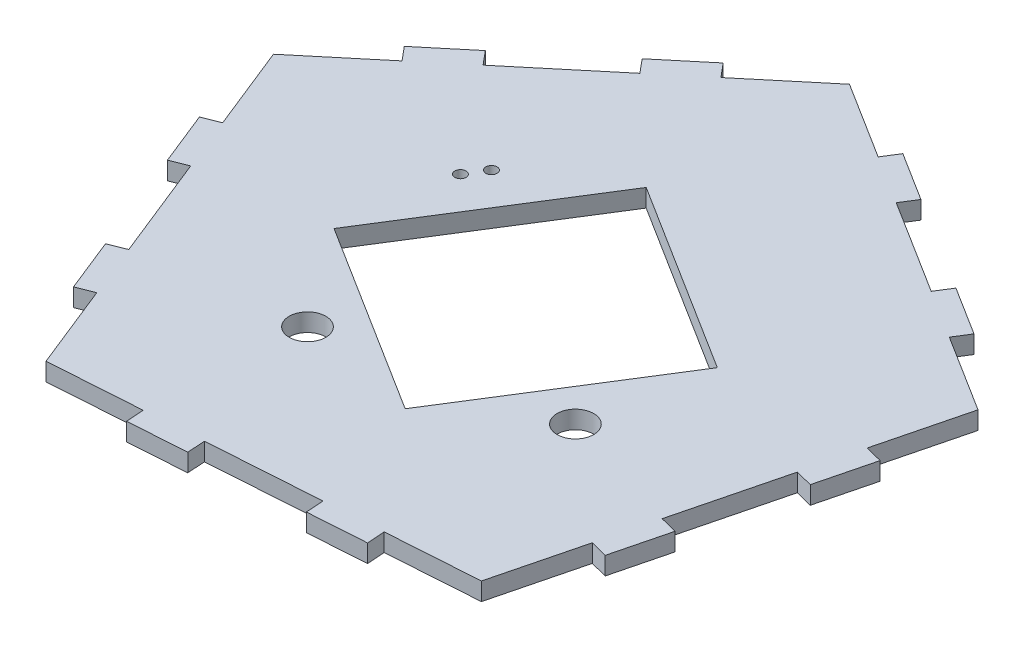
SolidWorks part; units mm, degrees
ref_plane "Front Plane" through (0, 0, 0) normal (0, 0, 1) x (1, 0, 0)
ref_plane "Top Plane" through (0, 0, 0) normal (0, 1, 0) x (1, 0, 0)
ref_plane "Right Plane" through (0, 0, 0) normal (1, 0, 0) x (0, 0, -1)
sketch "Sketch1" plane through (0, 0, 0) normal (0, 1, 0) x (1, 0, 0)
  line L1 (-59.9258, 15.1181) -> (-32.8962, -52.3211)
  line L2 (-32.8962, -52.3211) -> (39.5948, -47.4543)
  line L3 (39.5948, -47.4543) -> (57.3672, 22.9927)
  line L4 (57.3672, 22.9927) -> (-4.14, 61.6646)
  line L5 (-4.14, 61.6646) -> (-59.9258, 15.1181)
  circle A0 centre (0, 0) radius 50 construction
  dimension "D1" = 100
extrude "Boss-Extrude1" add sketch "Sketch1" along normal blind 3.18
ref_axis "Axis" through (0, 3.339, 0) along (0, -1, 0)
sketch "Axis Check" plane through (0, 3.18, 0) normal (0, 1, 0) x (1, 0, 0)
  line L0 (3.3493, -49.8877) -> (-4.14, 61.6646) construction
  line L1 (-32.8962, -52.3211) -> (39.5948, -47.4543) construction
  line L2 (57.3672, 22.9927) -> (-46.411, -18.6015) construction
  line L3 (-59.9258, 15.1181) -> (-32.8962, -52.3211) construction
  line L4 (-32.0329, 38.3913) -> (39.5948, -47.4543) construction
  line L5 (-4.14, 61.6646) -> (-59.9258, 15.1181) construction
  line L6 (-59.9258, 15.1181) -> (48.481, -12.2308) construction
  line L7 (39.5948, -47.4543) -> (57.3672, 22.9927) construction
  line L8 (-32.8962, -52.3211) -> (26.6136, 42.3287) construction
  line L9 (57.3672, 22.9927) -> (-4.14, 61.6646) construction
sketch "Sketch2" plane through (0, 0, 0) normal (0, -1, 0) x (1, 0, 0)
  line L0 (-53.8107, 0.1392) -> (-50.859, -1.0438)
  line L1 (-53.8107, 0.1392) -> (-50.1723, 9.2172)
  line L2 (-50.859, -1.0438) -> (-47.2205, 8.0342)
  line L3 (-50.1723, 9.2172) -> (-47.2205, 8.0342)
  line L4 (-59.9258, -15.1181) -> (-32.8962, 52.3211) construction
  line L5 (-42.6498, 27.9858) -> (-39.0113, 37.0638)
  line L6 (-42.6498, 27.9858) -> (-39.6981, 26.8028)
  line L7 (-39.0113, 37.0638) -> (-36.0596, 35.8808)
  line L8 (-39.6981, 26.8028) -> (-36.0596, 35.8808)
  line L9 (-46.411, 18.6015) -> (-19.2439, 7.7129) construction
  line L10 (-40.8306, 32.5248) -> (-37.8788, 31.3418) construction
  dimension "D1" = 3.18
  dimension "D2" = 9.78
  dimension "D3" = 10.11
extrude "Cut F" [suppressed] cut sketch "Sketch2" against normal through all
sketch "Sketch4" plane through (0, 3.18, 0) normal (0, 1, 0) x (1, 0, 0)
  line L9 (26.6136, 42.3287) -> (-26.6136, -42.3287) construction
  line L10 (57.3672, 22.9927) -> (-4.14, 61.6646) construction
  line L11 (-27.7286, -6.3206) -> (-6.3206, 27.7286)
  line L12 (-27.7286, -6.3206) -> (6.3206, -27.7286)
  line L13 (-6.3206, 27.7286) -> (27.7286, 6.3206)
  line L14 (6.3206, -27.7286) -> (27.7286, 6.3206)
  line L15 (-27.7286, -6.3206) -> (27.7286, 6.3206) construction
  line L16 (-6.3206, 27.7286) -> (6.3206, -27.7286) construction
  line L20 (0, 0) -> (39.0006, -24.5211) construction
  circle A0 centre (-14.9622, -23.7972) radius 3.25
  circle A1 centre (23.7972, -14.9622) radius 3.25
  point P5 (0, 0)
  point P6 (-14.9622, -23.7972)
  dimension "D3" = 6.5
  dimension "D1" = 40.22
  dimension "D2" = 40.22
  dimension "D4" = 8
  dimension "D5" = 8
extrude "Top Cut" cut sketch "Sketch4" against normal blind 10
sketch "Sketch7" plane through (0, 3.18, 0) normal (0, 1, 0) x (1, 0, 0)
  line L0 (0, 0) -> (26.6136, 42.3287) construction
  line L1 (57.3672, 22.9927) -> (-4.14, 61.6646) construction
  line L2 (1.0645, 1.6931) -> (-22.7326, 16.6553) construction
  line L3 (-6.1086, 1.4782) -> (-24.8617, 13.269) construction
  line L5 (-6.3206, 27.7286) -> (-27.7286, -6.3206) construction
  circle A0 centre (-22.7326, 16.6553) radius 1
  circle A1 centre (-24.8617, 13.269) radius 1
  dimension "D5" = 2
  dimension "D1" = 4
  dimension "D2" = 2
  dimension "D3" = 8
  dimension "D4" = 8
extrude "Top Cut 2" cut sketch "Sketch7" against normal through all
sketch "Bottom Cut" [suppressed] plane through (0, 3.18, 0) normal (0, 1, 0) x (1, 0, 0)
  line L0 (3.3493, -49.8877) -> (-4.14, 61.6646) construction
  line L2 (-32.8962, -52.3211) -> (39.5948, -47.4543) construction
  line L5 (-33.7535, -23.9959) -> (-33.7535, 24.3041) construction
  circle A4 centre (-33.7535, -23.9959) radius 1.6
  circle A5 centre (-32.1535, 24.3041) radius 1.6
  circle A6 centre (18.6465, 9.0041) radius 1.6
  circle A7 centre (18.6465, -18.8959) radius 1.6
  dimension "D1" = 3.2
  dimension "D4" = 27.9
  dimension "D3" = 5.1
  dimension "D2" = 48.3
  dimension "D5" = 50.8
sketch "Sketch3" plane through (0, 3.18, 0) normal (0, 1, 0) x (1, 0, 0)
  line L0 (0, 0) -> (-40.9819, 49.1167) construction
  line L1 (-49.5112, 27.9494) -> (-45.4366, 23.066)
  line L3 (-45.4366, 23.066) -> (-37.5894, 29.6135)
  line L4 (-41.664, 34.4969) -> (-37.5894, 29.6135)
  line L5 (-4.14, 61.6646) -> (-59.9258, 15.1181) construction
  line L6 (-71.9961, 5.0469) -> (-69.9588, 2.6052)
  line L7 (-71.9961, 5.0469) -> (-47.4739, 25.5077)
  line L14 (-26.4764, 47.1691) -> (-22.4018, 42.2857)
  line L16 (-22.4018, 42.2857) -> (-14.5546, 48.8333)
  line L17 (-18.6292, 53.7166) -> (-14.5546, 48.8333)
  line L18 (-42.539, 27.5695) -> (-41.513, 26.3398) construction
  line L19 (-49.5112, 27.9494) -> (-41.664, 34.4969)
  line L21 (-26.4764, 47.1691) -> (-18.6292, 53.7166)
  line L22 (-16.5919, 51.275) -> (4.7866, 69.1127)
  line L23 (-39.6267, 32.0552) -> (-24.4391, 44.7274)
  line M18 (-4.14, 61.6646) -> (-59.9258, 15.1181)
  dimension "D1" = 3.18
  dimension "D2" = 10.22
  dimension "D3" = 9.89
  dimension "D4" = 100
extrude "Extrude M" add sketch "Sketch3" against normal up to surface (3.18 mm away) contours L21 L14 L7 L17 | L19 L1 L4 M18 region at (-44.5689, 3.18, -30.0023) region at (-21.5341, 3.18, -49.222) up to face at (-22.7326, 0, -15.6553)
pattern_circular "Circle F" [suppressed] count 5 over 360 about axis through (0, 3.339, 0) along (0, -1, 0) of bodies 173
pattern_circular "Circle M" count 5 over 360 about axis through (0, 3.339, 0) along (0, -1, 0) of "Extrude M"
pattern_circular "Circle Side F" [suppressed] count 5 over 360 about axis through (0, 3.339, 0) along (0, -1, 0) of bodies 173
pattern_circular "Circle Side M" [suppressed] count 5 over 360 about axis through (0, 3.339, 0) along (0, -1, 0) of bodies 168
equation "\"kerf\"= .22mm"
equation "\"tabWidthF\"= 10 - \"kerf\""
equation "\"tabThickness\"= 3.18"
equation "\"D1@Sketch2\"=\"tabThickness\""
equation "\"tabWidthM\"= 10 + \"kerf\""
equation "\"halfkerf\"= \"kerf\" / 2.00mm"
equation "\"tabLength\" = \"kerf\" + 12"
